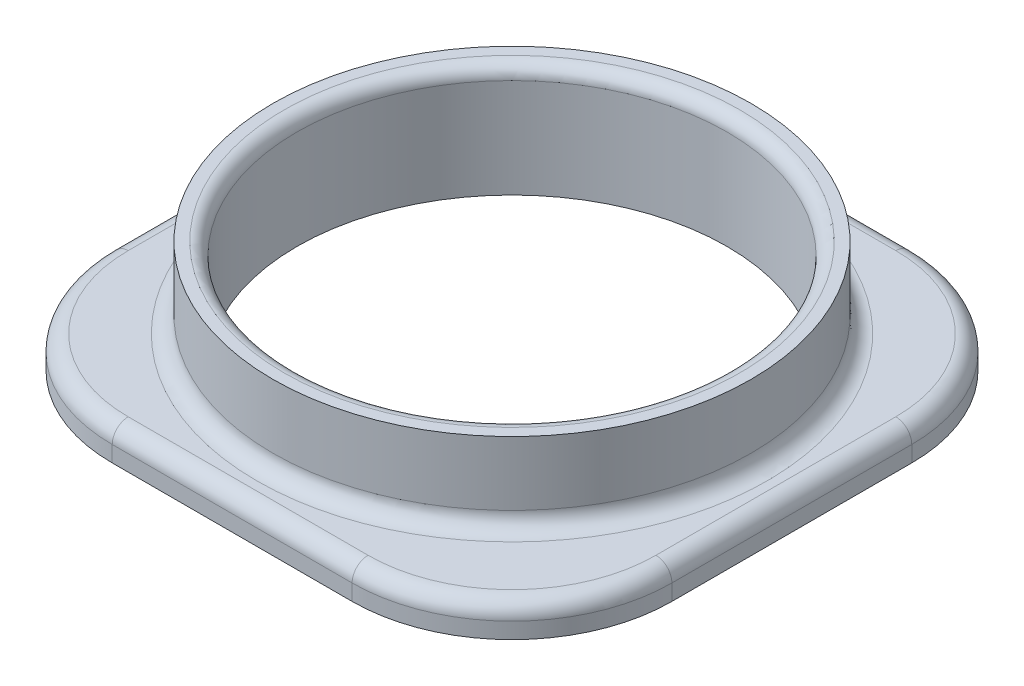
SolidWorks part; units mm, degrees
ref_plane "Front Plane" through (0, 0, 0) normal (0, 0, 1) x (1, 0, 0)
ref_plane "Top Plane" through (0, 0, 0) normal (0, 1, 0) x (1, 0, 0)
ref_plane "Right Plane" through (0, 0, 0) normal (1, 0, 0) x (0, 0, -1)
sketch "Sketch1" plane through (0, 0, 0) normal (0, 1, 0) x (1, 0, 0)
  circle A0 centre (0, 0) radius 13.45
  circle A1 centre (0, 0) radius 14.95
  dimension "D1" = 26.9
  dimension "D2" = 1.5
extrude "Boss-Extrude1" add sketch "Sketch1" along normal blind 5
sketch "Sketch2" plane through (0, 0, 0) normal (0, -1, 0) x (1, 0, 0)
  line L1 (-7.5, -17.5) -> (7.5, -17.5)
  line L2 (-17.5, -7.5) -> (-17.5, 7.5)
  line L3 (-7.5, 17.5) -> (7.5, 17.5)
  line L4 (17.5, -7.5) -> (17.5, 7.5)
  line L5 (-17.5, -17.5) -> (17.5, 17.5) construction
  line L6 (-17.5, 17.5) -> (17.5, -17.5) construction
  circle A0 centre (0, 0) radius 13.45
  arc A1 (-7.5, -17.5) -> (-17.5, -7.5) centre (-7.5, -7.5) cw
  arc A2 (7.5, -17.5) -> (17.5, -7.5) centre (7.5, -7.5) ccw
  arc A3 (7.5, 17.5) -> (17.5, 7.5) centre (7.5, 7.5) cw
  arc A4 (-17.5, 7.5) -> (-7.5, 17.5) centre (-7.5, 7.5) cw
  circle A5 centre (0, 0) radius 13.45 construction
  point P0 (0, 0)
  dimension "D3" = 10
  dimension "D4" = 0
  dimension "D1" = 35
  dimension "D2" = 35
extrude "Boss-Extrude2" add sketch "Sketch2" along normal blind 2
fillet "Fillet1" radius 0.8 1 edges at (0, 5, 13.45)
fillet "Fillet4" radius 1 9 edges at (0, 0, -17.5) (14.5711, 0, -14.5711) (17.5, 0, 0) (14.5711, 0, 14.5711) (0, 0, 17.5) (-14.5711, 0, 14.5711) (-17.5, 0, 0) (-14.5711, 0, -14.5711) (0, 0, 14.95)
